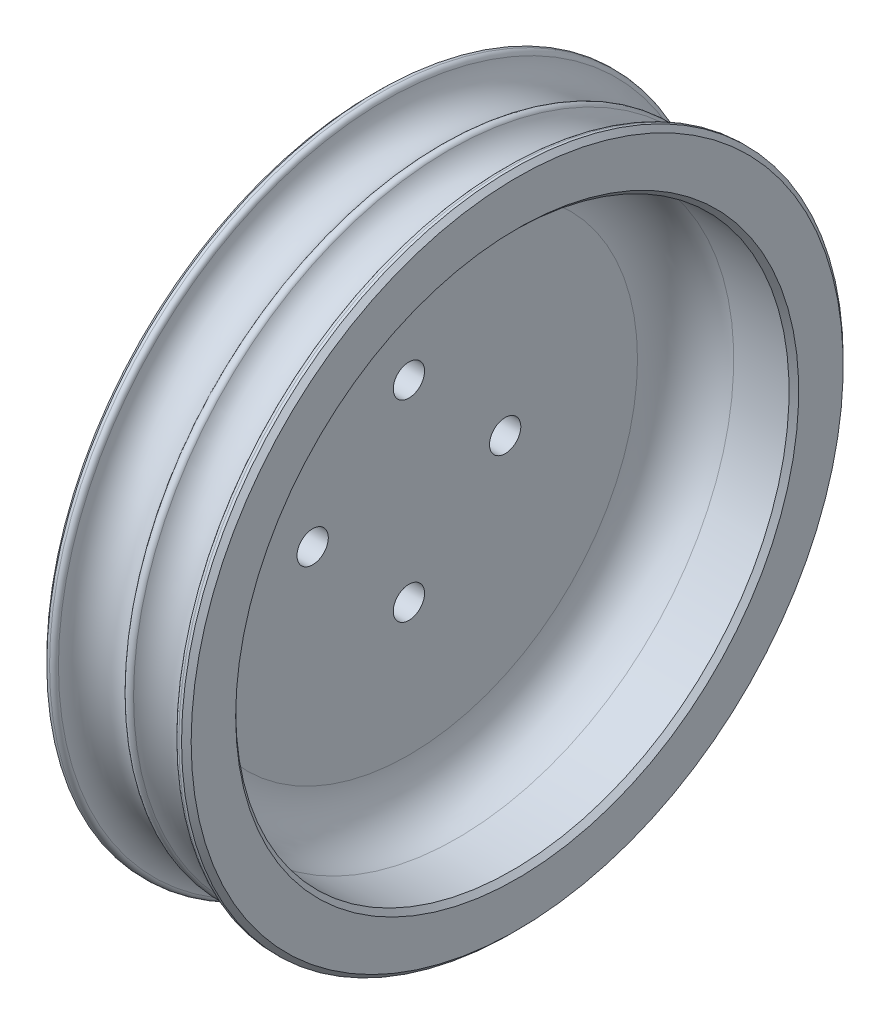
SolidWorks part; units mm, degrees
ref_plane "前视基准面" through (0, 0, 0) normal (0, 0, 1) x (1, 0, 0)
ref_plane "上视基准面" through (0, 0, 0) normal (0, 1, 0) x (1, 0, 0)
ref_plane "右视基准面" through (0, 0, 0) normal (1, 0, 0) x (0, 0, -1)
sketch "草图1" plane through (0, 0, 0) normal (0, 0, 1) x (1, 0, 0)
  line L0 (-16.5806, 0) -> (15.9821, 0) construction
  line L1 (0, 30.6673) -> (0, -24.0928) construction
  line L3 (6, 23) -> (0, 23)
  line L6 (5, 27.5) -> (6, 27.5)
  line L7 (6, 27.5) -> (6, 23)
  line L8 (-6, 23) -> (0, 23)
  line L9 (-6, 27.5) -> (-6, 23)
  line L10 (-5, 27.5) -> (-6, 27.5)
  arc A0 (0, 27.5) -> (5, 27.5) centre (2.5, 27.5) ccw
  arc A2 (0, 27.5) -> (-5, 27.5) centre (-2.5, 27.5) cw
  point P10 (3, 23)
  point P15 (-3, 23)
  dimension "D1" = 2.5
  dimension "D2" = 23
  dimension "D3" = 27.5
  dimension "D4" = 12
revolve "旋转1" add sketch "草图1" angle 360 about L0
fillet "圆角1" radius 0.4 3 edges at (-5, 0, 27.5) (5, 0, 27.5) (0, 0, 27.5)
sketch "草图4" plane through (-6, 0, 0) normal (-1, 0, 0) x (0, 0, 1)
  line L0 (-9.5031, 0) -> (8.9005, 0) construction
  circle A0 centre (0, 0) radius 23 construction
  circle A1 centre (0, 0) radius 23
  circle A2 centre (8, 0) radius 1.3
  circle A3 centre (0, -8) radius 1.3
  circle A4 centre (-8, 0) radius 1.3
  circle A5 centre (0, 8) radius 1.3
  point P16 (0, 0)
  dimension "D1" = 8
  dimension "D2" = 2.6
  dimension "D3" = 4
extrude "凸台-拉伸1" add sketch "草图4" against normal blind 3
chamfer "倒角1" distance 0.4 angle 45 7 edges at (6, 0, 23) (6, 0, 27.5) (-6, 0, 27.5) (-6, 0, 9.3) (-6, -8, 1.3) (-6, 0, -6.7) (-6, 8, 1.3)
ref_plane "基准面1" through (2.5, 0, 0) normal (1, 0, 0) x (0, 0, -1)
sketch "草图2" plane through (2.5, 0, 0) normal (1, 0, 0) x (0, 0, -1)
  circle A0 centre (0, 0) radius 27.5 construction
  dimension "D1" = 55
ref_plane "基准面3" through (-2.5, 0, 0) normal (-1, 0, 0) x (0, 0, 1)
sketch "草图3" plane through (-2.5, 0, 0) normal (-1, 0, 0) x (0, 0, 1)
  circle A0 centre (0, 0) radius 27.5 construction
  dimension "D1" = 55
fillet "圆角2" radius 4 1 edges at (-3, 0, 23)
